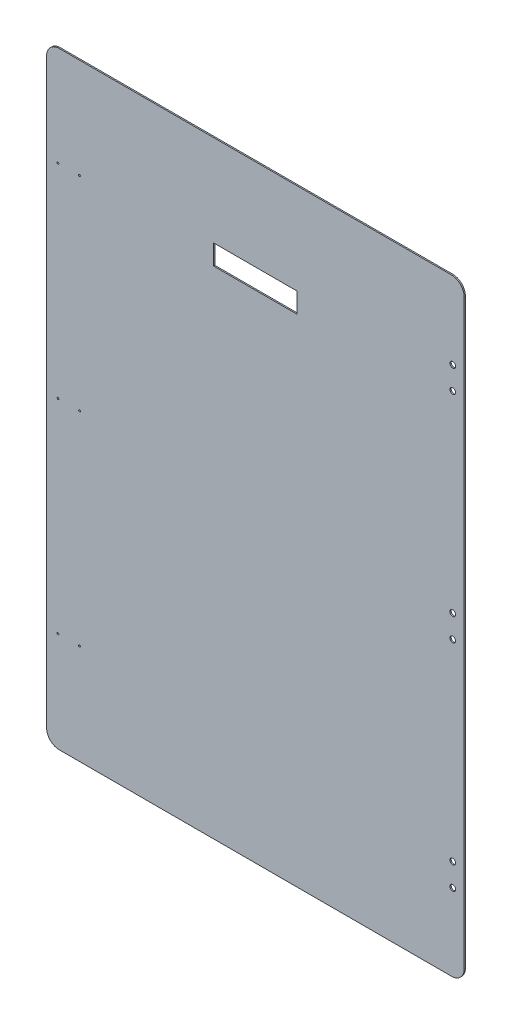
SolidWorks part; units mm, degrees
note: The reader was unsure of these and kept them because the rebuilt part matched: thickness of "Base-Flange1", "Sheet-Metal1", "Sheet-Metal5", "Sheet-Metal6", "Sheet-Metal7".
material "3.1255 (EN-AW 2014)"
ref_plane "Front Plane" through (0, 0, 0) normal (0, 0, 1) x (1, 0, 0)
ref_plane "Top Plane" through (0, 0, 0) normal (0, 1, 0) x (1, 0, 0)
ref_plane "Right Plane" through (0, 0, 0) normal (1, 0, 0) x (0, 0, -1)
sketch "Sketch1" plane through (0, 0, 0) normal (0, 0, 1) x (1, 0, 0)
  line L1 (310, -480) -> (-310, -480)
  line L2 (330, -460) -> (330, 460)
  line L3 (310, 480) -> (-310, 480)
  line L4 (-330, -460) -> (-330, 460)
  line L5 (330, -480) -> (-330, 480) construction
  line L6 (330, 480) -> (-330, -480) construction
  arc A0 (-310, -480) -> (-330, -460) centre (-310, -460) cw
  arc A1 (310, -480) -> (330, -460) centre (310, -460) ccw
  arc A2 (330, 460) -> (310, 480) centre (310, 460) ccw
  arc A3 (-310, 480) -> (-330, 460) centre (-310, 460) ccw
  point P0 (0, 0)
  dimension "D3" = 20
  dimension "D1" = 660
  dimension "D2" = 960
base flange "Base-Flange1" sketch "Sketch1" thickness 2 reverse thickness direction no parameters "D1"=2
hole_wizard "M8 Clearance Hole1" positions "Sketch5" profile "Sketch6" hole size "M8" standard "ISO" end condition through all
sketch "Sketch5" plane through (0, 0, 0) normal (0, 0, 1) x (1, 0, 0)
  point P0 (312, 358)
  point P3 (312, 322)
  point P6 (312, 18)
  point P9 (312, -18)
  point P12 (312, -322)
  point P15 (312, -358)
sketch "Sketch6" plane through (312, 358, 0) normal (1, 0, 0) x (0, -1, 0)
  line L0 (0, 0) -> (0, 2)
  line L1 (0, 2) -> (4.5, 2)
  line L2 (4.5, 2) -> (4.5, 0)
  line L5 (4.5, 0) -> (0, 0)
  line L11 (0, -6.35) -> (0, 107.95) construction
  dimension "Thru Hole Dia." = 9
  dimension "Thru Hole Depth" = 2
sketch "Sketch8" plane through (0, 0, 0) normal (0, 0, 1) x (1, 0, 0)
  line L0 (0, 0) -> (0, 320) construction
  line L1 (66, 304.15) -> (-66, 304.15)
  line L2 (66, 304.15) -> (66, 335.85)
  line L3 (66, 335.85) -> (-66, 335.85)
  line L4 (-66, 304.15) -> (-66, 335.85)
  line L5 (66, 304.15) -> (-66, 335.85) construction
  line L6 (66, 335.85) -> (-66, 304.15) construction
  point P0 (0, 320)
  dimension "D1" = 132
  dimension "D2" = 31.7
  dimension "D3" = 320
extrude "Cut-Extrude1" cut sketch "Sketch8" against normal blind 10
hole_wizard "M2.5 Clearance Hole2" positions "Sketch9" profile "Sketch10" hole size "M2.5" standard "ISO" end condition through all
sketch "Sketch9" plane through (0, 0, 0) normal (0, 0, 1) x (1, 0, 0)
  line L0 (-345, 328) -> (-345, 316) construction
  line L2 (-345, 322) -> (-312, 322) construction
  line L3 (-312, 322) -> (-278, 322) construction
  line L4 (-312, 322) -> (-312, 0) construction
  line L5 (-312, 0) -> (-312, -322) construction
  line L7 (-278, -322) -> (-278, 0) construction
  line L8 (-278, 0) -> (-278, 322) construction
  line L10 (0, 0) -> (-278, 0) construction
  line L11 (-278, 0) -> (-312, 0) construction
  point P8 (-312, 322)
  point P9 (-278, 322)
  point P16 (-312, 0)
  point P18 (-278, 0)
  point P20 (-312, -322)
  point P22 (-278, -322)
  dimension "D1" = 33
  dimension "D2" = 34
sketch "Sketch10" plane through (-278, -322, 0) normal (1, 0, 0) x (0, -1, 0)
  line L0 (0, 0) -> (0, 2)
  line L1 (0, 2) -> (1.45, 2)
  line L2 (1.45, 2) -> (1.45, 0)
  line L5 (1.45, 0) -> (0, 0)
  line L11 (0, -6.35) -> (0, 107.95) construction
  dimension "Thru Hole Dia." = 2.9
  dimension "Thru Hole Depth" = 2
sketch "Bend-Lines1" [suppressed] plane through (0, 0, 0) normal (0, 1, 0) x (1, 0, 0)
sketch "Bounding-Box1" [suppressed] plane through (0, 0, 0) normal (0, 1, 0) x (1, 0, 0)
sheet metal parameters "Sheet-Metal1" thickness 2 parameters "D1"=2, "D7"=1
flat pattern "Flat-Pattern1" [suppressed]
sketch "Bend-Lines2" plane through (0, 0, 0) normal (0, 1, 0) x (1, 0, 0)
sketch3d "Bounding-Box2" [suppressed]
  line L0 (650, -20, 0) -> (650, 950, 0) construction
  line L1 (-20, -20, 0) -> (-20, 950, 0) construction
  line L2 (650, -20, 0) -> (-20, -20, 0) construction
  line L3 (650, 950, 0) -> (-20, 950, 0) construction
sheet metal parameters "Sheet-Metal5" thickness 2 parameters "D1"=2, "D7"=1
flat pattern "Flat-Pattern1" [suppressed]
sketch "Bend-Lines2" plane through (0, 0, 0) normal (0, 1, 0) x (1, 0, 0)
sketch3d "Bounding-Box2" [suppressed]
  line L0 (640, -20, 0) -> (640, 940, 0) construction
  line L1 (-20, -20, 0) -> (-20, 940, 0) construction
  line L2 (640, -20, 0) -> (-20, -20, 0) construction
  line L3 (640, 940, 0) -> (-20, 940, 0) construction
sketch "Sketch4-1" [suppressed] plane through (0, 0, -2) normal (0, 0, -1) x (-1, 0, 0)
  circle A0 centre (-57.8297, 159.4791) radius 11.5
  dimension "D1" = 23
sheet metal parameters "Sheet-Metal6" thickness 2 parameters "D1"=2, "D7"=1
flat pattern "Flat-Pattern1"
sketch "Bend-Lines2" plane through (0, 0, 0) normal (0, 1, 0) x (1, 0, 0)
sketch3d "Bounding-Box2" [suppressed]
  line L0 (640, -20, 0) -> (640, 940, 0) construction
  line L1 (-20, -20, 0) -> (-20, 940, 0) construction
  line L2 (640, -20, 0) -> (-20, -20, 0) construction
  line L3 (640, 940, 0) -> (-20, 940, 0) construction
sheet metal parameters "Sheet-Metal7" thickness 2 parameters "D1"=2, "D7"=1
flat pattern "Flat-Pattern1"
sketch "Bend-Lines2" plane through (0, 0, 0) normal (0, 1, 0) x (1, 0, 0)
sketch3d "Bounding-Box2" [suppressed]
  line L0 (640, -20, 0) -> (640, 940, 0) construction
  line L1 (-20, -20, 0) -> (-20, 940, 0) construction
  line L2 (640, -20, 0) -> (-20, -20, 0) construction
  line L3 (640, 940, 0) -> (-20, 940, 0) construction
